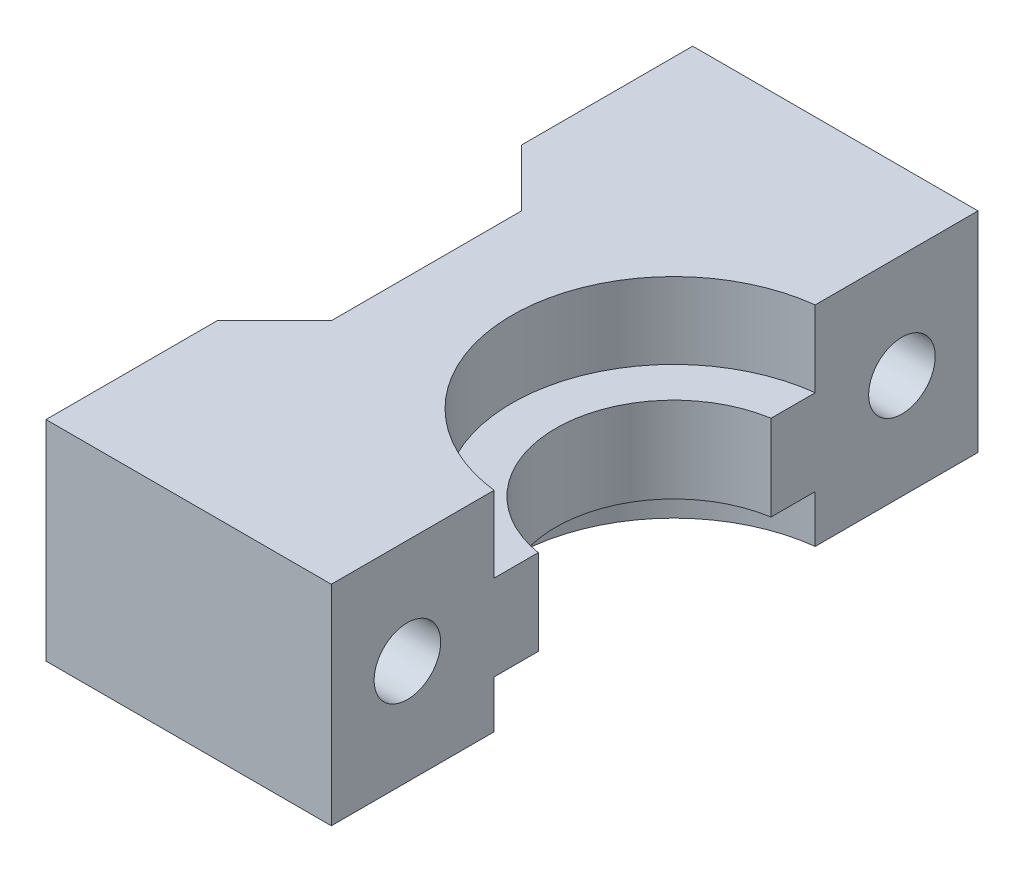
SolidWorks part; units mm, degrees
ref_plane "Front Plane" through (0, 0, 0) normal (0, 0, 1) x (1, 0, 0)
ref_plane "Top Plane" through (0, 0, 0) normal (0, 1, 0) x (1, 0, 0)
ref_plane "Right Plane" through (0, 0, 0) normal (1, 0, 0) x (0, 0, -1)
sketch "Sketch2" plane through (0, 0, 0) normal (1, 0, 0) x (0, 0, -1)
  line L0 (-30, 5.5) -> (-4, 5.5) construction
  line L1 (-34, 11) -> (0, 11)
  line L2 (-34, 11) -> (-34, 0)
  line L3 (-34, 0) -> (0, 0)
  line L4 (0, 11) -> (0, 0)
  line L5 (-17, 5.5) -> (-17, 0) construction
  circle A0 centre (-30, 5.5) radius 1.75
  circle A1 centre (-4, 5.5) radius 1.75
  dimension "D3" = 3.5
  dimension "D5" = 5.5
  dimension "D1" = 34
  dimension "D2" = 11
  dimension "D4" = 4
extrude "Boss-Extrude1" add sketch "Sketch2" against normal blind 16
sketch "Sketch4" plane through (0, 0, 0) normal (1, 0, 0) x (0, 0, -1)
  line L0 (-17, 0) -> (-17, 13.0278) construction
  line L1 (-34, 0) -> (0, 0) construction
  line L2 (-17, 0) -> (-25.5, 0)
  line L3 (-23.2, 7) -> (-23.2, 2.5)
  line L4 (-23.2, 7) -> (-25.5, 7)
  line L5 (-25.5, 7) -> (-25.5, 11)
  line L6 (-25.5, 11) -> (-17, 11)
  line L7 (-17, 11) -> (-17, 0)
  line L8 (0, 11) -> (-34, 11) construction
  line L9 (-23.2, 2.5) -> (-25.5, 2.5)
  line L10 (-25.5, 2.5) -> (-25.5, 0)
  line L12 (0, 11) -> (-34, 11) construction
  point P4 (-24.35, 7)
  dimension "D1" = 6.2
  dimension "D2" = 4.5
  dimension "D3" = 4
  dimension "D5" = 8.5
revolve "Cut-Revolve1" cut sketch "Sketch4" angle 360 about L0
sketch "Sketch5" plane through (0, 11, 0) normal (0, 1, 0) x (1, 0, 0)
  line L0 (-16, -34) -> (0, -34) construction
  line L1 (0, 0) -> (-1, 0)
  line L2 (0, 0) -> (0, -34)
  line L3 (0, -34) -> (-1, -34)
  line L4 (-1, 0) -> (-1, -34)
  line L5 (-16, 0) -> (-16, -34) construction
  line L6 (-16, -12) -> (-13, -12)
  line L7 (-16, -12) -> (-16, -22)
  line L8 (-16, -22) -> (-13, -22)
  line L9 (-13, -12) -> (-13, -22)
  point P13 (-16, -17)
  dimension "D1" = 1
  dimension "D2" = 3
  dimension "D3" = 10
extrude "Cut-Extrude1" cut sketch "Sketch5" against normal through all
chamfer "Chamfer1" distance 3 angle 45 2 edges at (-16, 5.5, 22) (-16, 5.5, 12)
